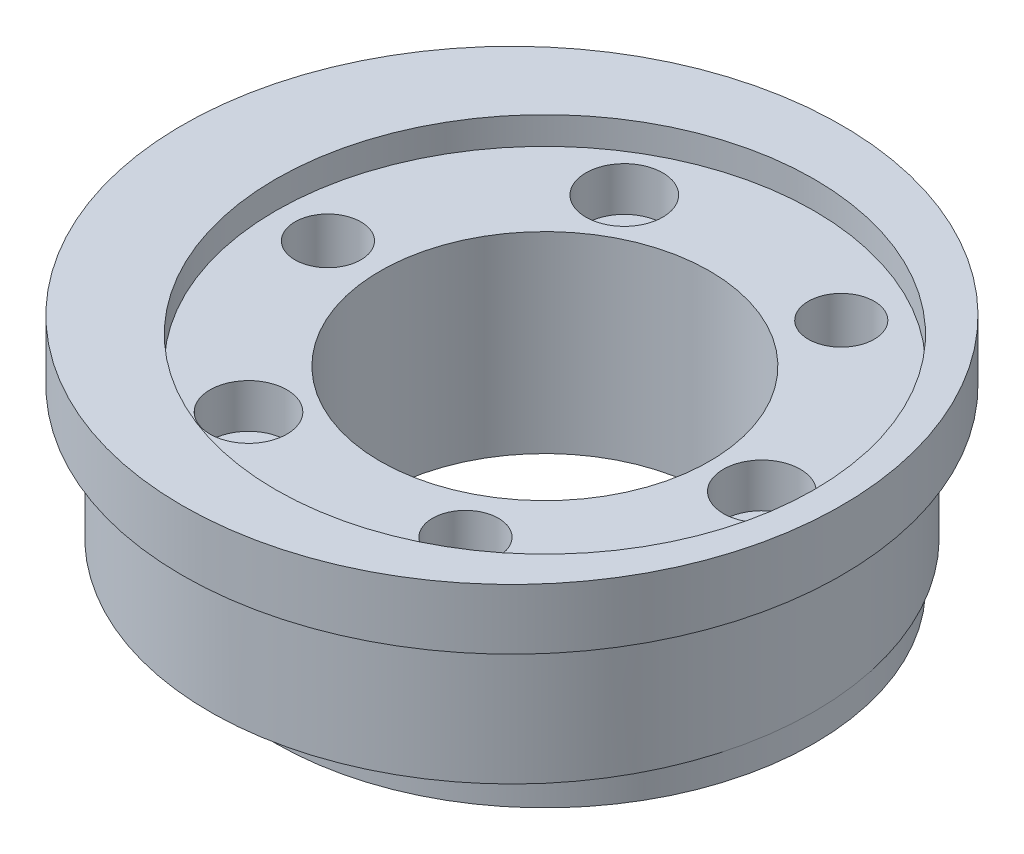
SolidWorks part; units mm, degrees
ref_plane "Front Plane" through (0, 0, 0) normal (0, 0, 1) x (1, 0, 0)
ref_plane "Top Plane" through (0, 0, 0) normal (0, 1, 0) x (1, 0, 0)
ref_plane "Right Plane" through (0, 0, 0) normal (1, 0, 0) x (0, 0, -1)
sketch "Sketch1" plane through (0, 0, 0) normal (0, 1, 0) x (1, 0, 0)
  circle A0 centre (0, 0) radius 27.5
extrude "Boss-Extrude1" add sketch "Sketch1" along normal blind 15
sketch "Sketch3" plane through (0, 15, 0) normal (0, 1, 0) x (1, 0, 0)
  line L0 (0, 0) -> (3, 0)
  line L1 (0, 0) -> (0, 27.5)
  line L2 (0, 0) -> (0, -27.5)
  circle A0 centre (3, 0) radius 24.5
  circle A1 centre (0, 0) radius 27.5
  point P5 (0, 24.3156)
  point P9 (0, -24.3156)
  circle M3 centre (0, 0) radius 27.5
extrude "Boss-Extrude3" add sketch "Sketch3" along normal blind 2.5 contours A0 L1 L2 M3 region at (-22.1149, 15, 0)
fillet "Fillet2" radius 1.5 4 edges at (0, 16.25, -27.5) (0, 16.25, -24.3156) (0, 16.25, 24.3156) (0, 16.25, 27.5)
sketch "Sketch4" plane through (0, 15, 0) normal (0, 1, 0) x (1, 0, 0)
  line L0 (0, 0) -> (3, 0)
  line L1 (-12, 0) -> (-21.5, 0)
  circle A2 centre (3, 0) radius 15
  arc A3 (-1.2404, 24.1303) -> (-1.2404, -24.1303) centre (3, 0) ccw construction
  circle A4 centre (-16.75, 0) radius 3
  circle A5 centre (12.875, 17.104) radius 3
  circle A6 centre (12.875, -17.104) radius 3
  point P23 (3, 0)
  dimension "D1" = 3
extrude "Cut-Extrude1" cut sketch "Sketch4" against normal blind 5 contours L1 A4 | L1 A4 | A5 | A6 region at (-16.75, 15, 1.2732) region at (-16.75, 15, -1.2732) region at (12.875, 15, -17.104) region at (12.875, 15, 17.104)
sketch "Sketch5" plane through (0, 15, 0) normal (0, 1, 0) x (1, 0, 0)
  line L0 (0, 0) -> (3, 0)
  circle A0 centre (3, 0) radius 15
extrude "Cut-Extrude2" cut sketch "Sketch5" against normal blind 15 contours A0 region at (-11.5757, 15, 0)
sketch "Sketch7" plane through (0, 0, 0) normal (0, -1, 0) x (1, 0, 0)
  line L0 (0, 0) -> (3, 0)
  line L1 (0, -27.5) -> (0, 27.5)
  circle A0 centre (3, 0) radius 24.5
  circle A1 centre (0, 0) radius 27.5 construction
  circle M2 centre (3, 0) radius 15
extrude "Boss-Extrude6" add sketch "Sketch7" along normal blind 2.5 contours A0 L1 M2 | L1 A0 M2 region at (-20.9683, 0, 0) region at (0.5619, 0, -19.5063)
sketch "Sketch8" plane through (0, 15, 0) normal (0, 1, 0) x (1, 0, 0)
  line L0 (0, 0) -> (3, 0)
  line L1 (1.5, 2.5981) -> (3, 0)
  line L2 (4.5, 2.5981) -> (3, 0)
  line L3 (6, 0) -> (3, 0)
  line L4 (4.5, -2.5981) -> (3, 0)
  line L5 (1.5, -2.5981) -> (3, 0)
  circle A0 centre (-16.75, 0) radius 2
  circle A1 centre (-6.875, 17.104) radius 2
  circle A2 centre (12.875, 17.104) radius 2
  circle A3 centre (22.75, 0) radius 2
  circle A4 centre (12.875, -17.104) radius 2
  circle A5 centre (-6.875, -17.104) radius 2
  point P23 (3, 0)
extrude "Cut-Extrude3" cut sketch "Sketch8" against normal blind 17.5 contours A1 | A5 | A3 region at (-6.875, 15, -17.104) region at (22.75, 15, 0) region at (-6.875, 15, 17.104)
sketch "Sketch9" plane through (0, 15, 0) normal (0, 1, 0) x (1, 0, 0)
  line L0 (0, 0) -> (3, 0)
  circle A0 centre (-6.875, 17.104) radius 3.5
  circle A1 centre (22.75, 0) radius 3.5
  circle A2 centre (-6.875, -17.104) radius 3.5
  point P12 (3, 0)
  circle M2 centre (-6.875, 17.104) radius 2
  circle M3 centre (-6.875, -17.104) radius 2
  circle M4 centre (22.75, 0) radius 2
extrude "Cut-Extrude4" cut sketch "Sketch9" against normal blind 4 contours A0 M2 | A1 M4 | A2 M3 region at (-10.276, 15, -17.104) region at (19.349, 15, 0) region at (-10.276, 15, 17.104)
sketch "Sketch10" plane through (0, 10, 0) normal (0, 1, 0) x (1, 0, 0)
  line L0 (0, 0) -> (3, 0)
  circle A0 centre (-16.75, 0) radius 2
  circle A1 centre (12.875, 17.104) radius 2
  circle A2 centre (12.875, -17.104) radius 2
  point P12 (3, 0)
extrude "Cut-Extrude5" cut sketch "Sketch10" against normal blind 2.5 contours A0 | A1 | A2 region at (-16.75, 10, 0) region at (12.875, 10, -17.104) region at (12.875, 10, 17.104)
sketch "Sketch14" plane through (0, 17.5, 0) normal (0, 1, 0) x (1, 0, 0)
  line L0 (0, 0) -> (3, 0)
  circle A3 centre (0, 0) radius 30
  circle A4 centre (0, 0) radius 27.5
  circle A5 centre (3, 0) radius 24.5
  line M3 (0, 25.6076) -> (0, 25.9567)
  arc M4 (0, 25.9567) -> (-1.5865, 27.4542) centre (-1.5, 25.9567) ccw
  arc M5 (-1.5865, 27.4542) -> (-1.5865, -27.4542) centre (0, 0) ccw
  arc M6 (-1.5865, -27.4542) -> (0, -25.9567) centre (-1.5, -25.9567) ccw
  line M7 (0, -25.9567) -> (0, -25.6076)
  arc M8 (0, -25.6076) -> (-1.2404, -24.1303) centre (-1.5, -25.6076) ccw
  arc M9 (-1.2404, -24.1303) -> (-1.2404, 24.1303) centre (3, 0) cw
  arc M10 (-1.2404, 24.1303) -> (0, 25.6076) centre (-1.5, 25.6076) ccw
extrude "Boss-Extrude14" add sketch "Sketch14" against normal blind 5.5 contours M10 M3 M4 M5 M6 M7 M8 M9 | A3 A4 M5 | A5 A4 M4 M3 M10 | A5 A4 M8 M7 M6 region at (-29.1515, 17.5, 0) region at (19.0111, 17.5, -19.0701) region at (18.6014, 17.5, 19.7074) region at (-0.8919, 17.5, -26.6009)
